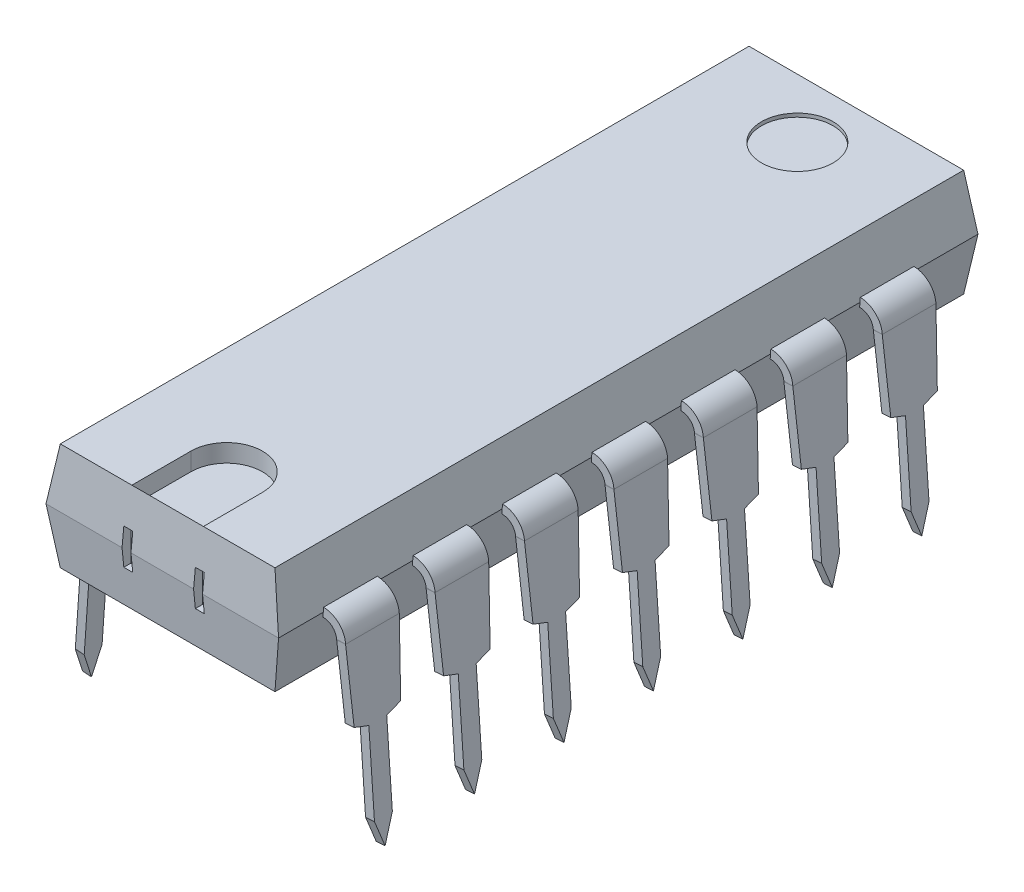
SolidWorks part; units mm, degrees
ref_plane "Front Plane" through (0, 0, 0) normal (0, 0, 1) x (1, 0, 0)
ref_plane "Top Plane" through (0, 0, 0) normal (0, 1, 0) x (1, 0, 0)
ref_plane "Right Plane" through (0, 0, 0) normal (1, 0, 0) x (0, 0, -1)
sketch "Sketch1" plane through (0, 0, 0) normal (0, 1, 0) x (1, 0, 0)
  line L0 (0, 9.625) -> (0, -9.625) construction
  line L1 (-3, 9.625) -> (3, 9.625)
  line L2 (-3, 9.625) -> (-3, -9.625)
  line L3 (-3, -9.625) -> (3, -9.625)
  line L4 (3, 9.625) -> (3, -9.625)
  line L5 (-3, 0) -> (3, 0) construction
  dimension "D1" = 6
  dimension "D2" = 19.25
ref_plane "Plane1" through (0, -1.5, 0) normal (0, 1, 0) x (1, 0, 0)
sketch "Sketch2" plane through (0, -1.5, 0) normal (0, 1, 0) x (1, 0, 0)
  line L1 (3.25, -9.775) -> (-3.25, -9.775)
  line L2 (3.25, -9.775) -> (3.25, 9.775)
  line L3 (3.25, 9.775) -> (-3.25, 9.775)
  line L4 (-3.25, -9.775) -> (-3.25, 9.775)
  line L5 (3.25, -9.775) -> (-3.25, 9.775) construction
  line L6 (3.25, 9.775) -> (-3.25, -9.775) construction
  point P0 (0, 0)
  dimension "D1" = 19.55
  dimension "D2" = 6.5
loft "Loft1" add profiles "Sketch1", "Sketch2" connector at (-3, 0, 9.625) connector at (-3.25, -1.5, 9.775)
mirror "Mirror1" about plane through (0, -1.5, 0) normal (0, 1, 0) of "Loft1"
ref_plane "Plane2" through (3.25, 0, 0) normal (1, 0, 0) x (0, 0, -1)
ref_plane "Plane3" through (0, 0, 9.775) normal (0, 0, 1) x (1, 0, 0)
sketch "Sketch3" plane through (0, 0, 9.775) normal (0, 0, 1) x (1, 0, 0)
  line L0 (0, 0) -> (0, -3) construction
  line L1 (-3, -3) -> (3, -3) construction
  line L2 (-3, 0) -> (0, 0) construction
  line L3 (-3, 0) -> (3, 0) construction
  line L4 (-1, 0) -> (-1, -3) construction
  line L5 (1, 0) -> (1, -3) construction
  line L6 (-3.25, -1.5) -> (3.25, -1.5) construction
  line L7 (-0.875, -2) -> (-1.125, -2)
  line L8 (-0.875, -2) -> (-0.875, -1)
  line L9 (-0.875, -1) -> (-1.125, -1)
  line L10 (-1.125, -2) -> (-1.125, -1)
  line L11 (-0.875, -2) -> (-1.125, -1) construction
  line L12 (-0.875, -1) -> (-1.125, -2) construction
  line L13 (0.875, -1) -> (1.125, -2) construction
  line L14 (0.875, -2) -> (1.125, -1) construction
  line L15 (1.125, -2) -> (1.125, -1)
  line L16 (0.875, -1) -> (1.125, -1)
  line L17 (0.875, -2) -> (0.875, -1)
  line L18 (0.875, -2) -> (1.125, -2)
  point P16 (-1, -1.5)
  point P25 (1, -1.5)
  dimension "D1" = 2
  dimension "D2" = 0.25
  dimension "D3" = 1
extrude "Cut-Extrude1" cut sketch "Sketch3" against normal blind 0.25
mirror "Mirror2" about plane through (0, 0, 0) normal (0, 0, 1) of "Cut-Extrude1"
ref_plane "Plane4" through (0, 0, 7.775) normal (0, 0, 1) x (1, 0, 0)
sketch "Sketch4" plane through (0, 0, 7.775) normal (0, 0, 1) x (1, 0, 0)
  line L0 (3.25, -8.0133) -> (3.25, 8.0133) construction
  line L1 (1.125, -1.5) -> (3.25, -1.5) construction
  line L2 (3.75, -2) -> (3.75, -4.5908) construction
  line L3 (3.7488, -1.9651) -> (4.1045, -7.0527)
  line L4 (1.125, -1.5) -> (3.25, -1.5) construction
  arc A0 (3.7488, -1.9651) -> (3.25, -1.5) centre (3.25, -2) ccw
  dimension "D1" = 1
  dimension "D2" = 4
  dimension "D3" = 5.1
ref_plane "Plane5" through (0, -7.0527, 0) normal (0, 1, 0) x (1, 0, 0)
sketch "Sketch5" plane through (0, -7.0527, 0) normal (0, 1, 0) x (1, 0, 0)
  line L0 (3.7488, -7.775) -> (4.1045, -7.775) construction
  line L1 (3.9795, -8.525) -> (4.2295, -8.525)
  line L2 (3.9795, -8.525) -> (3.9795, -7.025)
  line L3 (3.9795, -7.025) -> (4.2295, -7.025)
  line L4 (4.2295, -8.525) -> (4.2295, -7.025)
  line L5 (3.9795, -8.525) -> (4.2295, -7.025) construction
  line L6 (3.9795, -7.025) -> (4.2295, -8.525) construction
  point P0 (4.1045, -7.775)
  dimension "D1" = 0.25
  dimension "D2" = 1.5
sweep "Sweep1" add profiles "Sketch5" path "Sketch4"
sketch "Sketch6" plane through (3.7182, 0.26, 0) normal (0.9976, 0.0698, 0) x (0, 0, -1)
  line L1 (-7.525, -4.3761) -> (-7.125, -4.2306)
  line L2 (-8.025, -6.6306) -> (-8.025, -4.3761)
  line L3 (-8.025, -4.3761) -> (-7.525, -4.3761)
  line L4 (-7.525, -6.6306) -> (-7.525, -4.3761)
  line L5 (-7.775, -2.2306) -> (-7.775, -7.3174) construction
  line L6 (-8.525, -2.2306) -> (-7.025, -2.2306) construction
  line L7 (-7.775, -7.3174) -> (-8.025, -6.6306)
  line L8 (-7.775, -7.3174) -> (-7.525, -6.6306)
  line L9 (-8.025, -4.3761) -> (-8.425, -4.2306)
  line L10 (-8.525, -7.3306) -> (-8.525, -2.2306) construction
  line L11 (-8.525, -3.8306) -> (-8.525, -7.3306)
  line L12 (-8.525, -7.3306) -> (-7.025, -7.3306)
  line L13 (-7.025, -7.3306) -> (-7.025, -3.8306)
  line L14 (-8.525, -2.2306) -> (-8.425, -4.2306)
  line L15 (-7.025, -2.2306) -> (-7.125, -4.2306)
  point P10 (-7.775, -4.3761)
  line M7 (-7.025, -7.3306) -> (-7.025, -2.2306)
  line M9 (-8.525, -2.2306) -> (-8.525, -7.3306)
  line M10 (-8.525, -7.3306) -> (-7.025, -7.3306)
  dimension "D1" = 0.5
  dimension "D2" = 0.7
  dimension "D3" = 20
  dimension "D4" = 20
  dimension "D5" = 3.5
  dimension "D6" = 1.3
  dimension "D7" = 2
extrude "Cut-Extrude2" cut sketch "Sketch6" against normal up to surface (0.2494 mm away) contours L2 L9 L1 L4 L8 L7 M9 M10 M7 region at (4.0219, -4.0827, 7.3068) up to face at (3.8017, -4.5089, 7.775)
pattern_linear "LPattern1" count 7 spacing 2.5 along (0, 0, -1) of bodies 106
mirror "Mirror3" about plane through (0, 0, 0) normal (1, 0, 0) of bodies 106 107 108 109 110 111 112
sketch "Sketch7" plane through (0, 0, 0) normal (0, 1, 0) x (1, 0, 0)
  line L0 (0, 9.625) -> (0, -9.625) construction
  line L1 (-3, -9.625) -> (3, -9.625) construction
  line L2 (-3.2587, 7.975) -> (3.25, 7.975) construction
  line L3 (3.25, -9.775) -> (3.25, 9.775) construction
  line L4 (-3, 0) -> (3, 0) construction
  line L5 (-3, 9.625) -> (-3, -9.625) construction
  line L6 (3, -9.625) -> (3, 9.625) construction
  line L7 (-1, -7.975) -> (1, -7.975) construction
  line L9 (-1, -7.975) -> (-1, -9.625)
  line L10 (-1, -9.625) -> (1, -9.625)
  line L11 (1, -7.975) -> (1, -9.625)
  circle A0 centre (0, 7.975) radius 1
  arc A1 (-1, -7.975) -> (1, -7.975) centre (0, -7.975) cw
  dimension "D1" = 2
extrude "Cut-Extrude3" cut sketch "Sketch7" against normal blind 0.5 contours A1 L9 L11 region at (0, 0, 8.3971)
extrude "Cut-Extrude4" cut sketch "Sketch7<3>" against normal blind 0.1 contours A0 region at (0, 0, -7.975)
sketch "Sketch7<3>" plane through (0, 0, 0) normal (0, 1, 0) x (1, 0, 0) same geometry as "Sketch7"
